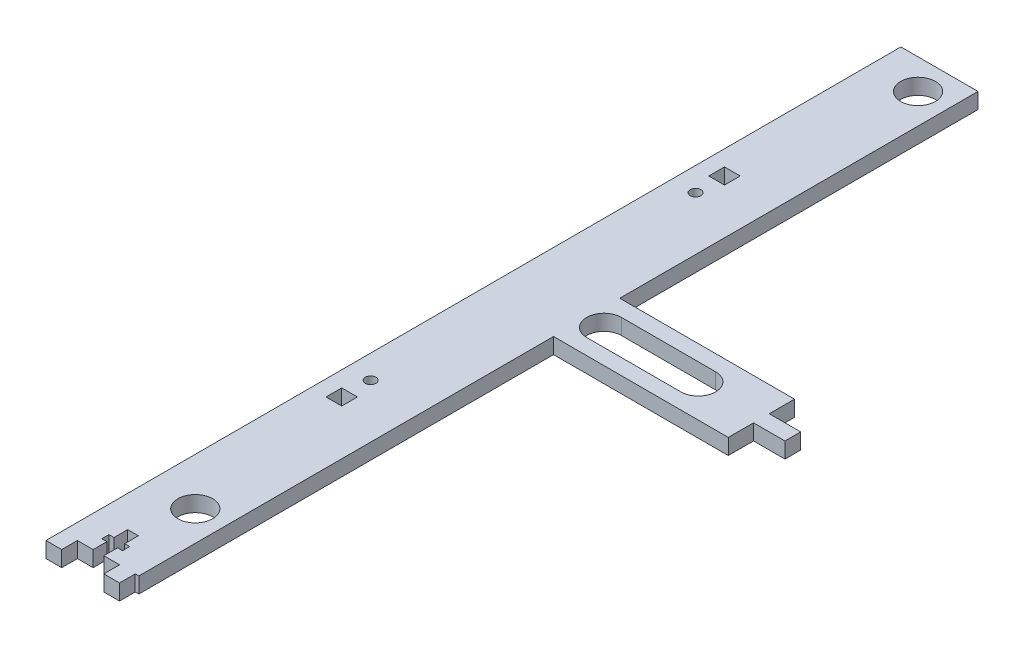
SolidWorks part; units mm, degrees
ref_plane "Front Plane" through (0, 0, 0) normal (0, 0, 1) x (1, 0, 0)
ref_plane "Top Plane" through (0, 0, 0) normal (0, 1, 0) x (1, 0, 0)
ref_plane "Right Plane" through (0, 0, 0) normal (1, 0, 0) x (0, 0, -1)
sketch "Axle Support Plate" plane through (0, 0, 0) normal (0, 1, 0) x (1, 0, 0)
  line L0 (19.05, 146.05) -> (19.05, -146.05) construction
  line L1 (6.35, 158.1601) -> (6.35, -187.325) construction
  line L2 (6.35, -80.518) -> (6.35, -74.168)
  line L3 (6.35, 80.518) -> (12.7, 80.518)
  line L4 (31.1601, -180.975) -> (31.1601, -13.3801)
  line L5 (0, 0) -> (31.1601, 158.1601) construction
  line L6 (0, 0) -> (31.1601, -180.975) construction
  line L8 (0, 158.1601) -> (31.1601, 158.1601)
  line L9 (6.35, -180.975) -> (12.7, -180.975)
  line L10 (6.35, 80.518) -> (6.35, 74.168)
  line L11 (6.35, 74.168) -> (12.7, 74.168)
  line L12 (0, -187.325) -> (0, 158.1601)
  line L13 (12.7, 80.518) -> (12.7, 74.168)
  line L14 (6.35, -80.518) -> (12.7, -80.518)
  line L15 (12.7, -80.518) -> (12.7, -74.168)
  line L16 (6.35, -74.168) -> (12.7, -74.168)
  line L17 (31.1601, 0) -> (0, 0) construction
  line L18 (0, -187.325) -> (6.35, -187.325)
  line L19 (6.35, -187.325) -> (6.35, -180.975)
  line L20 (23.368, -180.975) -> (23.368, -187.325)
  line L21 (23.368, -187.325) -> (29.718, -187.325)
  line L22 (29.718, -187.325) -> (29.718, -180.975)
  line L23 (29.718, -180.975) -> (31.1601, -180.975)
  line L24 (9.525, 80.518) -> (9.525, 65.659) construction
  line L25 (12.7, -180.975) -> (12.7, -175.44)
  line L26 (12.7, -175.44) -> (10.659, -175.44)
  line L27 (10.659, -175.44) -> (10.659, -172.54)
  line L28 (10.659, -172.54) -> (12.7, -172.54)
  line L29 (12.7, -172.54) -> (12.7, -167.005)
  line L30 (12.7, -167.005) -> (17.018, -167.005)
  line L31 (17.018, -167.005) -> (17.018, -172.54)
  line L32 (17.018, -172.54) -> (19.059, -172.54)
  line L33 (19.059, -172.54) -> (19.059, -175.44)
  line L34 (19.059, -175.44) -> (17.018, -175.44)
  line L35 (17.018, -175.44) -> (17.018, -180.975)
  line L36 (17.018, -180.975) -> (23.368, -180.975)
  line L37 (31.1601, 13.3801) -> (101.7805, 13.3801)
  line L38 (101.7805, 13.3801) -> (101.7805, 3.175)
  line L39 (101.7805, -13.3801) -> (31.1601, -13.3801)
  line L40 (38.1903, 0) -> (76.2903, 0) construction
  line L41 (38.1903, 7.0301) -> (76.2903, 7.0301)
  line L42 (38.1903, -7.0301) -> (76.2903, -7.0301)
  line L43 (101.7805, -3.175) -> (114.4805, -3.175)
  line L44 (114.4805, -3.175) -> (114.4805, 3.175)
  line L45 (114.4805, 3.175) -> (101.7805, 3.175)
  line L46 (31.1601, 13.3801) -> (31.1601, 158.1601)
  line L47 (31.1601, 13.3801) -> (31.1601, -13.3801) construction
  line L48 (31.1601, 0) -> (114.4805, 0) construction
  line L51 (101.7805, -3.175) -> (101.7805, -13.3801)
  circle A0 centre (19.05, 146.05) radius 7.0301
  circle A1 centre (19.05, -146.05) radius 7.0301
  circle A2 centre (9.525, 65.659) radius 2.159
  circle A3 centre (9.525, -65.659) radius 2.159
  arc A4 (38.1903, 7.0301) -> (38.1903, -7.0301) centre (38.1903, 0) ccw
  arc A5 (76.2903, -7.0301) -> (76.2903, 7.0301) centre (76.2903, 0) ccw
  point P0 (0, 0)
  point P15 (19.05, 0)
  point P38 (9.525, 67.818)
  point P57 (57.2403, 0)
  dimension "D1" = 5.08
  dimension "D4" = 14.0603
  dimension "D5" = 5.08
  dimension "D8" = 63.5
  dimension "D14" = 14.0603
  dimension "D15" = 4.318
  dimension "D16" = 6.35
  dimension "D22" = 7.0301
  dimension "D25" = 25.4903
  dimension "D2" = 292.1
  dimension "D3" = 6.35
  dimension "D6" = 12.7
  dimension "D7" = 6.35
  dimension "D9" = 6.35
  dimension "D10" = 6.35
  dimension "D11" = 6.35
  dimension "D12" = 13.97
  dimension "D13" = 34.925
  dimension "D17" = 4.318
  dimension "D18" = 8.4
  dimension "D19" = 2.9
  dimension "D20" = 6.35
  dimension "D21" = 6.35
  dimension "D23" = 6.35
  dimension "D24" = 38.1
  dimension "D26" = 12.7
  dimension "D27" = 6.35
extrude "Boss-Extrude1" add sketch "Axle Support Plate" along normal blind 6.35
equation "\"Ball Diameter\"= 1.75in"
equation "\"Sheet Thickness\"= 0.25in"
equation "\"Screw Diameter\"= .17in"
equation "\"Robot Diameter\"= 14in"
equation "\"Castor Screw Diameter\"= 0.22in"
equation "\"Wheel Diameter\" = 4in"
equation "\"Nut Diameter\" = 8.4mm"
equation "\"Nut Height\" = 2.9mm"
equation "\"Screw Height\" = 0.55in"
equation "\"Pulley Diameter\" = 1in"
equation "\"Reactor Height\" = 14in"
equation "\"Elevator Height\" = 11.5in"
equation "\"Elevator Width\" = \"Ball Diameter\" + 0.25in"
equation "\"D2@Axle Support Plate\"=\"Elevator Height\""
equation "\"D1@Boss-Extrude1\"=\"Sheet Thickness\""
equation "\"Elevator Bearing Diameter\" = sqr(2*(\"Sheet Thickness\"^2)) + 0.2in"
equation "\"Elevator Axle Length\" = \"Elevator Width\" + 6*\"Sheet Thickness\""
equation "\"D4@Axle Support Plate\"=\"Elevator Bearing Diameter\""
equation "\"D6@Axle Support Plate\"=(\"Pulley Diameter\")/2"
equation "\"D3@Axle Support Plate\"=\"Sheet Thickness\""
equation "\"D7@Axle Support Plate\"=\"Sheet Thickness\""
equation "\"D10@Axle Support Plate\"=\"Sheet Thickness\""
equation "\"D11@Axle Support Plate\"=\"Sheet Thickness\""
equation "\"D12@Axle Support Plate\"=\"Screw Height\""
equation "\"D13@Axle Support Plate\"=2.5in - \"Sheet Thickness\" - (\"Ball Diameter\")/2"
equation "\"D9@Axle Support Plate\"=\"Sheet Thickness\""
equation "\"D14@Axle Support Plate\"=\"Elevator Bearing Diameter\""
equation "\"D15@Axle Support Plate\"=\"Screw Diameter\""
equation "\"D16@Axle Support Plate\"=\"Sheet Thickness\""
equation "\"D17@Axle Support Plate\"=\"Screw Diameter\""
equation "\"D18@Axle Support Plate\"=\"Nut Diameter\""
equation "\"D19@Axle Support Plate\"=\"Nut Height\""
equation "\"D20@Axle Support Plate\"=\"Sheet Thickness\""
equation "\"D21@Axle Support Plate\"=\"Sheet Thickness\""
equation "\"D22@Axle Support Plate\"=\"Elevator Bearing Diameter\"/2"
equation "\"D23@Axle Support Plate\"=\"Sheet Thickness\""
equation "\"Elevator Axle Endcap Diameter\" = \"Elevator Bearing Diameter\" + 0.25in"
equation "\"D25@Axle Support Plate\"=\"Elevator Axle Endcap Diameter\"+0.2in"
equation "\"D27@Axle Support Plate\"=\"Sheet Thickness\""
